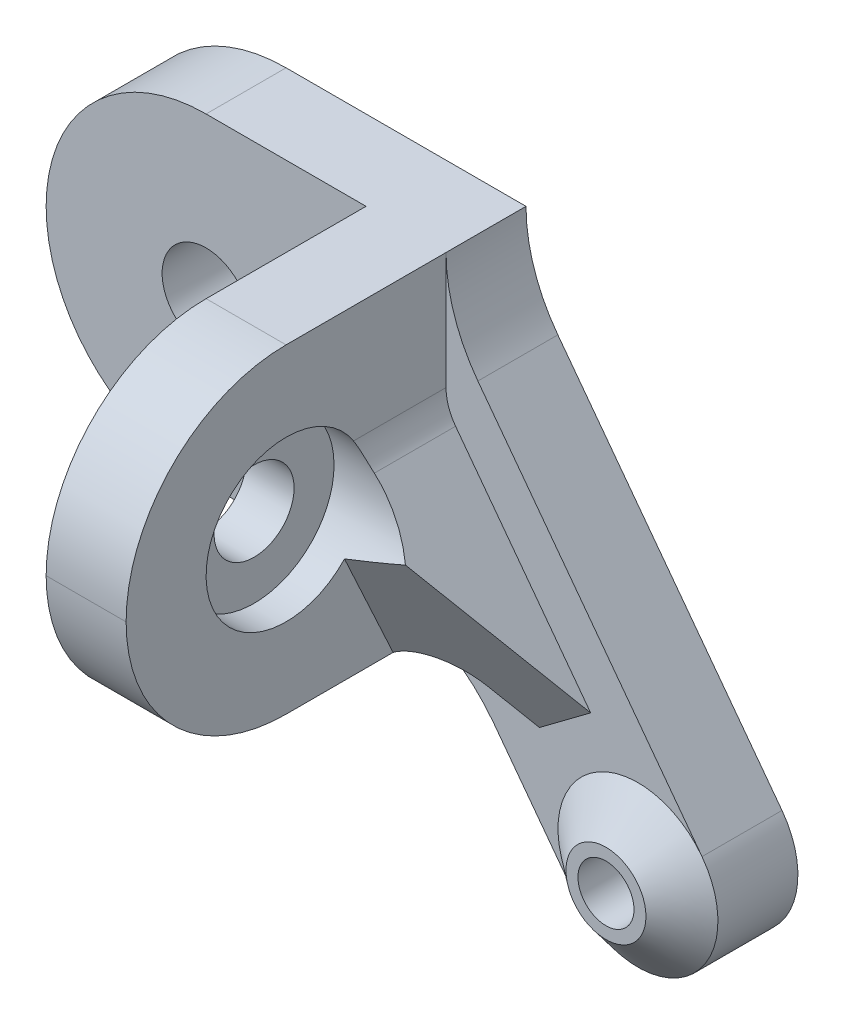
SolidWorks part; units mm, degrees
material "ABS"
ref_plane "Front Plane" through (0, 0, 0) normal (0, 0, 1) x (1, 0, 0)
ref_plane "Top Plane" through (0, 0, 0) normal (0, 1, 0) x (1, 0, 0)
ref_plane "Right Plane" through (0, 0, 0) normal (1, 0, 0) x (0, 0, -1)
sketch "Sketch1" plane through (0, 0, 0) normal (0, 1, 0) x (1, 0, 0)
  line L0 (0, 0) -> (0, -25)
  line L1 (0, -25) -> (5, -25)
  line L2 (5, -25) -> (5, -5)
  line L3 (5, -5) -> (47, -5)
  line L4 (47, -5) -> (47, 0)
  line L5 (47, 0) -> (0, 0)
  line L6 (25, 8.7838) -> (25, -25.5405) construction
  line L7 (42, 7.9279) -> (42, -15.6757) construction
  dimension "D1" = 20
  dimension "D2" = 20
  dimension "D3" = 5
  dimension "D4" = 17
  dimension "D5" = 5
extrude "Boss-Extrude1" add sketch "Sketch1" along normal blind 32.7
sketch "Sketch2" plane through (5, 0, 0) normal (1, 0, 0) x (0, 0, -1)
  line L0 (-25, 32.7) -> (-5, 32.7) construction
  line L1 (-25, 32.7) -> (-25, 0) construction
  circle A0 centre (-15, 22.7) radius 2.75
  point P2 (0, 0)
  dimension "D1" = 10
  dimension "D2" = 10
  dimension "D3" = 5.5
extrude "Cut-Extrude1" cut sketch "Sketch2" against normal blind 10
sketch "Sketch3" plane through (0, 0, 5) normal (0, 0, 1) x (1, 0, 0)
  line L0 (5, 32.7) -> (5, 0) construction
  line L2 (5, 32.7) -> (47, 32.7) construction
  circle A0 centre (15, 22.7) radius 2.75
  point P7 (0, 0)
  dimension "D1" = 5.5
  dimension "D2" = 10
  dimension "D3" = 10
extrude "Cut-Extrude2" cut sketch "Sketch3" against normal blind 10
sketch "Sketch4" plane through (0, 0, 0) normal (1, 0, 0) x (0, 0, -1)
  circle A0 centre (-15, 22.7) radius 5.5
  dimension "D1" = 11
extrude "Cut-Extrude3" cut sketch "Sketch4" along normal blind 1
sketch "Sketch5" plane through (0, 0, 0) normal (0, 0, -1) x (-1, 0, 0)
  circle A0 centre (-15, 22.7) radius 5.5
  dimension "D1" = 11
extrude "Cut-Extrude4" cut sketch "Sketch5" against normal blind 1
sketch "Sketch6" plane through (0, 0, 0) normal (0, 0, -1) x (-1, 0, 0)
  line L1 (-5, 0) -> (-47, 0) construction
  line L2 (-47, 32.7) -> (-47, 0) construction
  circle A0 centre (-42, 5) radius 1.75
  circle A1 centre (-15, 22.7) radius 2.75 construction
  point P4 (0, 0)
  dimension "D2" = 3.5
  dimension "D1" = 27
  dimension "D3" = 5
  dimension "D4" = 5
extrude "Cut-Extrude5" cut sketch "Sketch6" against normal blind 12
sketch "Sketch7" plane through (0, 0, 5) normal (0, 0, 1) x (1, 0, 0)
  circle A0 centre (42, 5) radius 1.75
  circle A1 centre (42, 5) radius 2.5
  dimension "D1" = 5
extrude "Boss-Extrude2" add sketch "Sketch7" along normal blind 2
chamfer "Chamfer2" distance 2.5 distance2 2 1 edges at (39.5, 5, 5) first distance on face at (26, 16.35, 5)
sketch "Sketch9" plane through (0, 0, 5) normal (0, 0, 1) x (1, 0, 0)
  line L0 (5, 0) -> (42, 0) construction
  line L1 (25, 0) -> (30, 0)
  line L2 (25, 0) -> (25, 32.7)
  line L3 (25, 32.7) -> (30, 32.7)
  line L4 (30, 0) -> (30, 32.7)
  line L5 (5, 32.7) -> (47, 32.7) construction
  line L6 (5, 32.7) -> (5, 0) construction
  dimension "D1" = 20
  dimension "D2" = 5
extrude "Boss-Extrude3" add sketch "Sketch9" along normal blind 20
sketch "Sketch10" plane through (0, 0, 5) normal (0, 0, 1) x (1, 0, 0)
  line L0 (5, 12.7) -> (30, 12.7)
  line L1 (0, 32.7) -> (0, 0) construction
  line L2 (30, 0) -> (30, 32.7) construction
  line L3 (30, 12.7) -> (37.9955, 2.006)
  line L4 (5, 32.7) -> (25, 32.7) construction
  line L5 (46.0045, 7.994) -> (30, 29.4)
  line L6 (30, 0) -> (30, 32.7) construction
  line L7 (30, 29.4) -> (30, 32.7)
  line L8 (0, 12.7) -> (0, -0.8812)
  line L9 (0, -0.8812) -> (49.6865, -0.8812)
  line L10 (49.6865, -0.8812) -> (49.6865, 32.7)
  line L11 (49.6865, 32.7) -> (30, 32.7)
  line L12 (5, 32.7) -> (5, 0) construction
  line L13 (0, 32.7) -> (5, 32.7)
  line L14 (0, 32.7) -> (0, 12.7)
  line L16 (5, 32.7) -> (5, 12.7)
  arc A0 (47, 5) -> (42, 0) centre (42, 5) ccw construction
  arc A1 (37.9955, 2.006) -> (46.0045, 7.994) centre (42, 5) ccw
  dimension "D1" = 20
extrude "Cut-Extrude7" cut sketch "Sketch10" against normal through all both and the other way through all
ref_plane "Plane1" through (29.3382, 21.9351, 0) normal (0.8009, 0.5988, 0) x (0, 0, -1)
sketch "Sketch11" plane through (29.3382, 21.9351, 0) normal (0.8009, 0.5988, 0) x (0, 0, -1)
  line L0 (-3.9877, -15.2869) -> (-15.005, 3.8252)
  line L1 (-15.005, 3.8252) -> (-3.9877, 3.8252)
  line L2 (-3.9877, 3.8252) -> (-3.9877, -15.2869)
  point P2 (-3.9877, -15.2869)
extrude "Boss-Extrude4" add sketch "Sketch11" along normal blind 2 and the other way blind 2
sketch "Sketch12" plane through (30, 0, 0) normal (1, 0, 0) x (0, 0, -1)
  line L0 (-5, 12.7) -> (-25, 12.7) construction
  line L1 (-25, 12.7) -> (-25, 32.7) construction
  circle A0 centre (-15, 22.7) radius 5
  dimension "D3" = 10
  dimension "D1" = 10
  dimension "D2" = 10
extrude "Cut-Extrude8" cut sketch "Sketch12" against normal blind 2 and the other way blind 22
sketch "Sketch13" plane through (28, 0, 0) normal (1, 0, 0) x (0, 0, -1)
  circle A0 centre (-15, 22.7) radius 2.5
  dimension "D1" = 5
extrude "Cut-Extrude9" cut sketch "Sketch13" against normal blind 12
fillet "Fillet2" radius 10 6 edges at (30, 12.7, 2.5) (30, 29.4, 2.5) (5, 32.7, 2.5) (5, 12.7, 2.5) (27.5, 32.7, 25) (27.5, 12.7, 25)
fillet "Fillet3" radius 3 2 edges at (30, 17.71, 7.8104) (30, 24.39, 7.6471)
equation "\"D3@Sketch6\"=\"D4@Sketch6\""
equation "\"D2@Sketch12\"=\"D1@Sketch12\""
